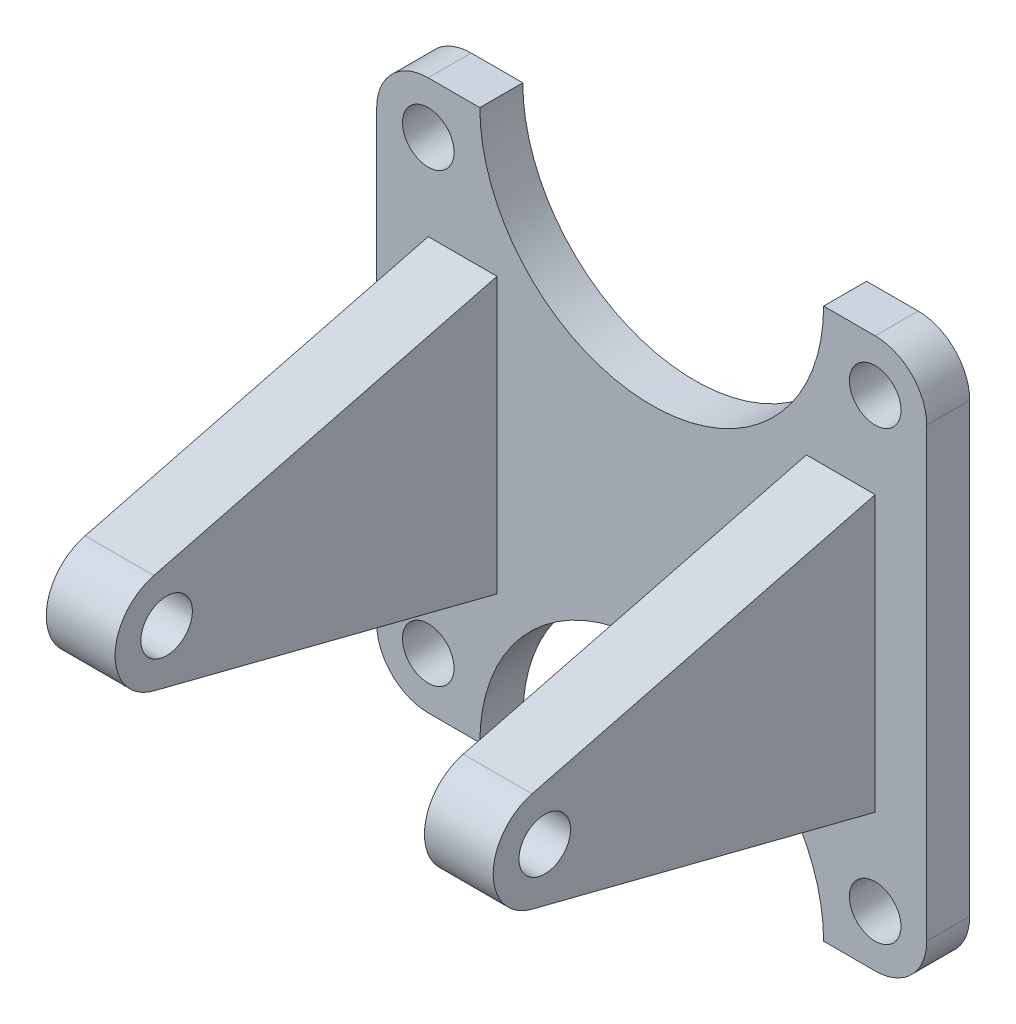
SolidWorks part; units mm, degrees
ref_plane "前视基准面" through (0, 0, 0) normal (0, 0, 1) x (1, 0, 0)
ref_plane "上视基准面" through (0, 0, 0) normal (0, 1, 0) x (1, 0, 0)
ref_plane "右视基准面" through (0, 0, 0) normal (1, 0, 0) x (0, 0, -1)
other "Configuration Table"
sketch "草图1" plane through (0, 0, 0) normal (0, 0, 1) x (1, 0, 0)
  line L0 (0, -0.3558) -> (0, -50000.3558) construction
  line L1 (13, 13) -> (-13, 13)
  line L2 (13, 13) -> (13, -13)
  line L3 (13, -13) -> (-13, -13)
  line L4 (-13, 13) -> (-13, -13)
  line L5 (13, 13) -> (-13, -13) construction
  line L6 (13, -13) -> (-13, 13) construction
  line L7 (13, 16) -> (-13, 16)
  line L8 (16, 13) -> (16, -13)
  line L9 (13, -16) -> (-13, -16)
  line L10 (-16, 13) -> (-16, -13)
  line L11 (16, 16) -> (-16, -16) construction
  line L12 (16, -16) -> (-16, 16) construction
  line L13 (0, 0) -> (-50000, 0) construction
  line L15 (13, 6) -> (13, -6)
  line L18 (-13, -8) -> (-9, -8)
  line L19 (-13, 8) -> (-13, -8)
  line L20 (-13, 8) -> (-9, 8)
  line L21 (-9, 8) -> (-9, -8)
  line L22 (13, 8) -> (13, -8)
  line L23 (13, 8) -> (9, 8)
  line L24 (9, 8) -> (9, -8)
  line L25 (13, -8) -> (9, -8)
  circle A0 centre (13, 13) radius 1.5
  circle A1 centre (-13, 13) radius 1.5
  circle A2 centre (13, -13) radius 1.5
  circle A3 centre (-13, -13) radius 1.5
  arc A4 (16, -13) -> (13, -16) centre (13, -13) cw
  arc A5 (-13, -16) -> (-16, -13) centre (-13, -13) cw
  arc A6 (-16, 13) -> (-13, 16) centre (-13, 13) cw
  arc A7 (13, 16) -> (16, 13) centre (13, 13) cw
  arc A8 (-10, 16) -> (10, 16) centre (0, 16) ccw
  arc A9 (-10, -16) -> (10, -16) centre (0, -16) cw
  point P0 (0, 0)
  point P10 (0, 0)
  dimension "D3" = 3
  dimension "D6" = 3
  dimension "D10" = 10
  dimension "D1" = 26
  dimension "D2" = 26
  dimension "D4" = 32
  dimension "D5" = 32
  dimension "D9" = 13
  dimension "D11" = 5
  dimension "D12" = 4
  dimension "D13" = 5
extrude "凸台-拉伸1" add sketch "草图1" along normal blind 25 contours L21 L20 L4 L18 | L25 L2 L23 L24 region at (-11, 0, 0) region at (11, 0, 0)
extrude "凸台-拉伸2" add sketch "草图1<4>" along normal blind 2.5 contours L3 A9 A2 L2 L25 L24 L23 A0 L1 A8 A1 L4 L20 L21 L18 A3 | L9 A9 L3 A3 L4 A1 L1 A8 L7 A6 L10 A5 | L3 A9 L9 A4 L8 A7 L7 A8 L1 A0 L2 A2 region at (-14.0243, 0, 0) region at (0, 0, 0) region at (14.0243, 0, 0)
sketch "草图1<4>" plane through (0, 0, 0) normal (0, 0, 1) x (1, 0, 0) same geometry as "草图1"
sketch "草图5" plane through (-13, 0, 0) normal (-1, 0, 0) x (0, 0, 1)
  line L0 (2.5, 8) -> (33.8586, 0)
  line L2 (33.8586, 0) -> (2.5, -8)
  circle A0 centre (21.7225, 0) radius 3
  circle A1 centre (21.7225, 0) radius 1.5
  point P3 (0, 0)
  point P4 (19.7093, 0)
  point P9 (21.7225, 0)
  line M7 (25, 8) -> (2.5, 8)
  line M9 (2.5, -8) -> (25, -8)
  line M10 (25, -8) -> (25, 8)
  dimension "D1" = 3
  dimension "D2" = 6
extrude "切除-拉伸1" cut sketch "草图5" against normal through all contours L0 M7 M10 | L2 M10 M9 | A0 L2 L0 M10 | A1 region at (-13, 6.0866, 17.5) region at (-13, 2.522, 23.7163) region at (-13, -6.0866, 17.5) region at (-13, 0, 21.7225)
